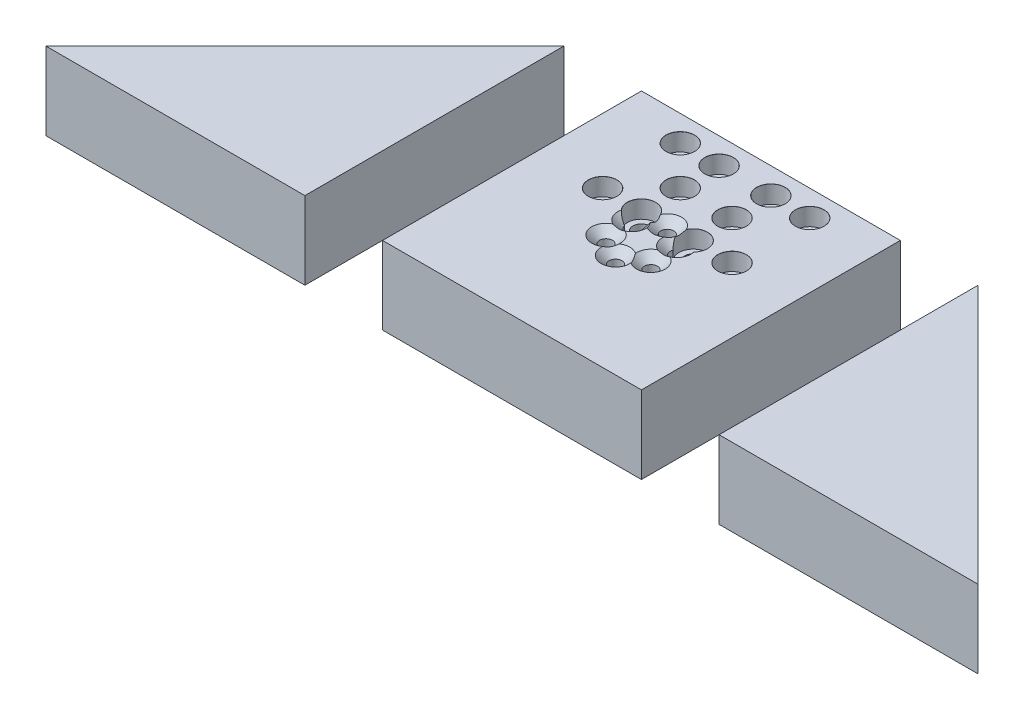
SolidWorks part; units mm, degrees
ref_plane "前视基准面" through (0, 0, 0) normal (0, 0, 1) x (1, 0, 0)
ref_plane "上视基准面" through (0, 0, 0) normal (0, 1, 0) x (1, 0, 0)
ref_plane "右视基准面" through (0, 0, 0) normal (1, 0, 0) x (0, 0, -1)
other "Configuration Table"
sketch "草图1" plane through (0, 0, 0) normal (0, 1, 0) x (1, 0, 0)
  line L0 (80, -50) -> (180, -50)
  line L1 (-50, -50) -> (50, -50)
  line L2 (-50, -50) -> (-50, 50)
  line L3 (-50, 50) -> (50, 50)
  line L4 (50, -50) -> (50, 50)
  line L5 (0, 50) -> (0, -50) construction
  line L6 (-50, 0) -> (50, 0) construction
  line L7 (180, -50) -> (80, 50)
  line L8 (80, 50) -> (80, -50)
  point P0 (0, 0)
  point P6 (73.8189, 35.8018)
  dimension "D1" = 100
  dimension "D2" = 30
extrude "凸台-拉伸1" add sketch "草图1" along normal blind 30
sketch "草图7" plane through (0, 30, 0) normal (0, 1, 0) x (1, 0, 0)
  line L0 (50, 50) -> (-50, 50) construction
  line L1 (-50, 50) -> (-50, -50) construction
  point P0 (-25, 10)
  point P9 (-25.5241, 7.9107)
  point P10 (0, 0)
  point P13 (0, 0)
  point P14 (0, 0)
  point P15 (0, 0)
  point P16 (0, 0)
  dimension "D1" = 40
  dimension "D2" = 25
hole_wizard "M6 六角圆柱头螺钉的柱形沉头孔2" positions "草图7" profile "草图6" counterbore size "M6" standard "GB" end condition through all
sketch "草图6" plane through (-25, 30, -10) normal (1, 0, 0) x (0, 0, 1)
  line L0 (0, 0) -> (0, 30)
  line L1 (0, 30) -> (3.3, 30)
  line L3 (3.3, 30) -> (3.3, 6.8)
  line L4 (5.5, 6.8) -> (3.3, 6.8)
  line L5 (5.5, 6.8) -> (5.5, 0.025)
  line L6 (5.5, 0.025) -> (5.525, 0)
  line L7 (5.525, 0) -> (0, 0)
  line L8 (-5.5, 0.025) -> (-5.525, 0) construction
  line L11 (0, -6.35) -> (0, 107.95) construction
  dimension "通孔孔直径" = 6.6
  dimension "通孔孔深度" = 30
  dimension "柱形沉头孔直径" = 11
  dimension "柱形沉头孔深度" = 6.8
  dimension "近端锥形沉头孔直径" = 11.05
  dimension "近端锥形沉头孔角度" = 90
sketch "草图15" plane through (0, 30, 0) normal (0, 1, 0) x (1, 0, 0)
  line L0 (-25, 10) -> (0, 10)
  line L2 (0, 0) -> (0, 10)
  point P0 (0, 10)
hole_wizard "M6 螺纹孔2" positions "草图15" profile "草图14" tap size "M6" standard "GB" end condition through all
sketch "草图14" plane through (0, 30, -10) normal (1, 0, 0) x (0, 0, 1)
  line L0 (0, 0) -> (0, 30)
  line L1 (0, 30) -> (2.5, 30)
  line L2 (2.5, 30) -> (2.5, 3.025)
  line L3 (2.5, 3.025) -> (5.525, 0)
  line L5 (5.525, 0) -> (0, 0)
  line L6 (-2.5, 3.025) -> (-5.525, 0) construction
  line L11 (0, -6.35) -> (0, 107.95) construction
  dimension "通孔螺纹孔钻头直径" = 5
  dimension "通孔螺纹孔钻头深度" = 30
  dimension "近端锥形沉头孔直径" = 11.05
  dimension "近端锥形沉头孔角度" = 90
cosmetic thread "孔螺纹线3" parameters "D2"=6
pattern_linear "阵列(线性)1" count 2 spacing 15 along (1, 0, 0) count 3 spacing 15 along (0, 0, -1) skipping (0, 1) of "M6 六角圆柱头螺钉的柱形沉头孔2"
ref_axis "基准轴1" through (0, 0, 0) along (0, 1, 0)
pattern_circular "阵列(圆周)1" count 6 over 360 about axis through (0, 0, 0) along (0, 1, 0) of "M6 螺纹孔2"
mirror "镜向1" about plane through (0, 0, 0) normal (1, 0, 0) of "阵列(线性)1"
mirror "镜向3" about plane through (0, 0, 0) normal (1, 0, 0) of bodies 107
